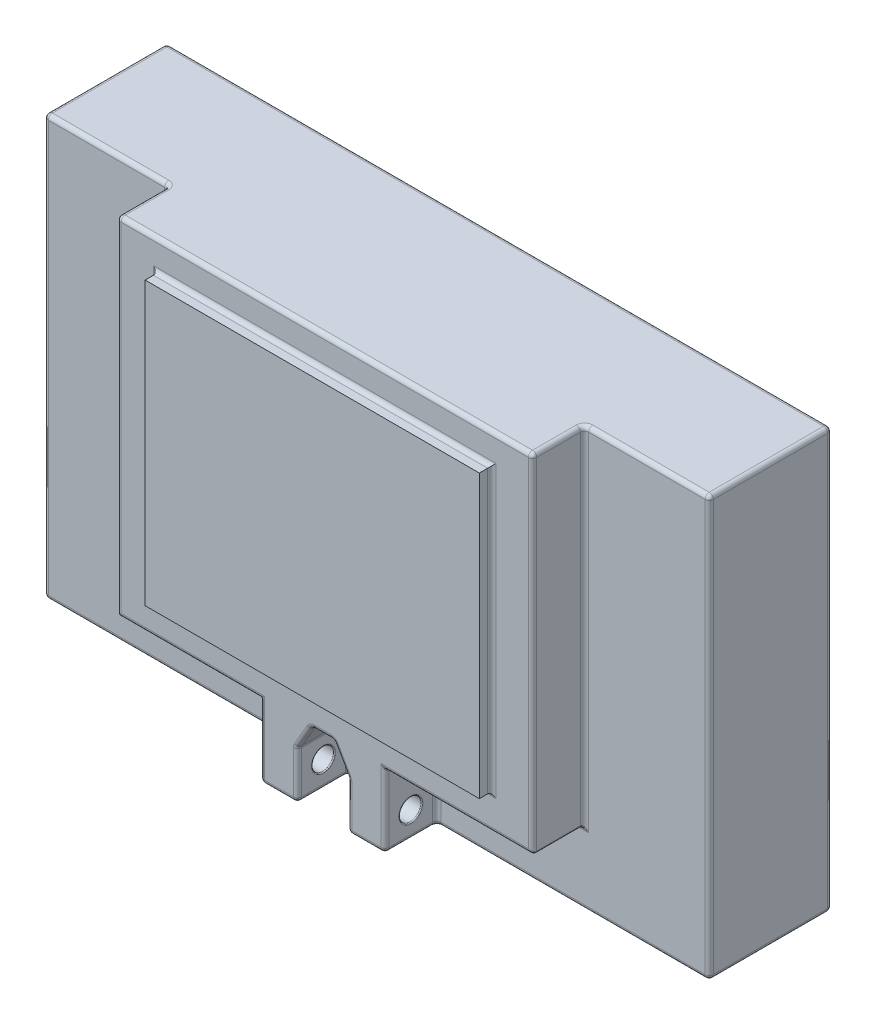
SolidWorks part; units mm, degrees
ref_plane "Front Plane" through (0, 0, 0) normal (0, 0, 1) x (1, 0, 0)
ref_plane "Top Plane" through (0, 0, 0) normal (0, 1, 0) x (1, 0, 0)
ref_plane "Right Plane" through (0, 0, 0) normal (1, 0, 0) x (0, 0, -1)
sketch "Sketch1" plane through (0, 0, 0) normal (0, 0, 1) x (1, 0, 0)
  line L1 (0, 0) -> (320, 0)
  line L2 (0, 0) -> (0, 202)
  line L3 (0, 202) -> (320, 202)
  line L4 (320, 0) -> (320, 202)
  dimension "D1" = 320
  dimension "D2" = 202
extrude "Boss-Extrude1" add sketch "Sketch1" along normal blind 84
sketch "Sketch2" plane through (0, 0, 84) normal (0, 0, 1) x (1, 0, 0)
  line L0 (320, 202) -> (0, 202) construction
  line L1 (240.4, 187.7) -> (79.6, 187.7)
  line L2 (240.4, 187.7) -> (240.4, 52)
  line L3 (240.4, 52) -> (79.6, 52)
  line L4 (79.6, 187.7) -> (79.6, 52)
  line L5 (160, 187.7) -> (160, 202) construction
  dimension "D1" = 14.3
  dimension "D2" = 160.8
  dimension "D3" = 135.7
sketch "Sketch3" plane through (0, 202, 0) normal (0, 1, 0) x (1, 0, 0)
  line L0 (320, -84) -> (0, -84) construction
  line L1 (260, -84) -> (320, -84)
  line L2 (260, -84) -> (260, -59)
  line L3 (260, -59) -> (320, -59)
  line L4 (320, -84) -> (320, -59)
  line L5 (320, -84) -> (320, 0) construction
  dimension "D1" = 25
  dimension "D2" = 60
extrude "Cut-Extrude2" cut sketch "Sketch3" against normal blind 280
sketch "Sketch4" plane through (0, 202, 0) normal (0, 1, 0) x (1, 0, 0)
  line L1 (0, -84) -> (60, -84)
  line L2 (0, -84) -> (0, -59)
  line L3 (0, -59) -> (60, -59)
  line L4 (60, -84) -> (60, -59)
  dimension "D1" = 25
  dimension "D2" = 60
extrude "Cut-Extrude3" cut sketch "Sketch4" against normal blind 280
sketch "Sketch5" plane through (60, 0, 0) normal (-1, 0, 0) x (0, 0, 1)
  line L0 (84, 202) -> (84, 0) construction
  line L1 (59, 0) -> (84, 0)
  line L2 (59, 0) -> (59, 35)
  line L3 (59, 35) -> (84, 35)
  line L4 (84, 0) -> (84, 35)
  dimension "D1" = 35
extrude "Cut-Extrude4" cut sketch "Sketch5" against normal blind 280
sketch "Sketch6" plane through (0, 0, 59) normal (0, 0, 1) x (1, 0, 0)
  line L1 (320, 0) -> (320, 202) construction
  line L2 (0, 0) -> (0, 202) construction
  line L3 (320, 0) -> (0, 0) construction
  line L4 (60, 202) -> (0, 202) construction
  point P0 (13, 187.9)
  point P1 (13, 14.1)
  point P2 (307, 14.1)
  point P3 (307, 187.9)
  dimension "D1" = 294
  dimension "D2" = 13
  dimension "D3" = 13
  dimension "D4" = 13
  dimension "D5" = 13
  dimension "D6" = 14.1
  dimension "D7" = 14.1
  dimension "D8" = 14.1
sketch "Sketch8" plane through (0, 0, 59) normal (0, 0, 1) x (1, 0, 0)
  line L0 (320, 0) -> (0, 0) construction
  line L1 (128.9599, 0) -> (188.9599, 0)
  line L2 (128.9599, 0) -> (128.9599, 35)
  line L3 (128.9599, 35) -> (188.9599, 35)
  line L4 (188.9599, 0) -> (188.9599, 35)
  line L5 (260, 35) -> (60, 35) construction
  dimension "D1" = 60
extrude "Boss-Extrude2" add sketch "Sketch8" along normal up to surface (25 mm away) up to face at (160, 118.5, 84)
sketch "Sketch9" plane through (0, 0, 84) normal (0, 0, 1) x (1, 0, 0)
  line L0 (146.9099, 0) -> (146.9099, 23)
  line L1 (188.9599, 0) -> (128.9599, 0) construction
  line L2 (146.9099, 23) -> (153.8381, 35)
  line L3 (153.8381, 35) -> (164.0817, 35)
  line L4 (164.0817, 35) -> (171.0099, 23)
  line L5 (171.0099, 23) -> (171.0099, 0)
  line L6 (128.9599, 35) -> (60, 35) construction
  line L7 (128.9599, 0) -> (128.9599, 35) construction
  line L9 (171.0099, 0) -> (146.9099, 0)
  dimension "D1" = 24.1
  dimension "D2" = 17.95
  dimension "D3" = 120
  dimension "D4" = 120
  dimension "D5" = 23
  dimension "D6" = 23
extrude "Cut-Extrude5" cut sketch "Sketch9" against normal up to surface (25 mm away) up to face at (256.32, 79, 59)
extrude "Boss-Extrude3" add sketch "Sketch2" along normal blind 6
fillet "Fillet1" radius 2 17 edges at (171.0099, 11.5, 84) (171.0099, 0, 71.5) (167.5458, 29, 84) (171.0099, 23, 71.5) (158.9599, 35, 84) (164.0817, 35, 71.5) (150.374, 29, 84) (153.8381, 35, 71.5) (146.9099, 0, 71.5) (146.9099, 11.5, 84) (146.9099, 23, 71.5) (146.9099, 11.5, 59) (150.374, 29, 59) (158.9599, 35, 59) (167.5458, 29, 59) (171.0099, 11.5, 59) (158.9599, 0, 59)
fillet "Fillet2" radius 2 16 edges at (254.48, 0, 59) (320, 101, 59) (260, 202, 71.5) (290, 202, 59) (0, 101, 59) (60, 202, 71.5) (30, 202, 59) (60, 118.5, 59) (260, 118.5, 59) (224.48, 35, 59) (94.48, 35, 59) (64.48, 0, 59) (188.9599, 0, 71.5) (188.9599, 17.5, 59) (128.9599, 0, 71.5) (128.9599, 17.5, 59)
fillet "Fillet3" radius 2 19 edges at (171.5957, 0.5858, 83.4142) (146.3241, 0.5858, 83.4142) (160, 187.7, 84) (79.6, 119.85, 84) (160, 52, 84) (240.4, 119.85, 84) (224.48, 35, 84) (188.9599, 18.5, 84) (188.3741, 0.5858, 84) (179.9849, 0, 84) (137.9349, 0, 84) (129.5457, 0.5858, 84) (128.9599, 18.5, 84) (94.48, 35, 84) (60, 117.5, 84) (60.5858, 201.4142, 84) (160, 202, 84) (259.4142, 201.4142, 84) (260, 117.5, 84)
fillet "Fillet4" radius 2 12 edges at (319.4142, 0.5858, 58.4142) (319.4142, 201.4142, 58.4142) (0.5858, 201.4142, 58.4142) (0.5858, 0.5858, 58.4142) (320, 0, 28.5) (320, 202, 28.5) (160, 0, 0) (320, 101, 0) (160, 202, 0) (0, 101, 0) (0, 202, 28.5) (0, 0, 28.5)
sketch "Sketch10" plane through (128.9599, 0, 0) normal (-1, 0, 0) x (0, 0, 1)
  line L0 (71.5, 12.3886) -> (71.5, 0) construction
  line L1 (82, 0) -> (61, 0) construction
  circle A0 centre (71.5, 12.3886) radius 5.25
  dimension "D1" = 10.5
extrude "Cut-Extrude6" cut sketch "Sketch10" against normal blind 68
fillet "Fillet5" radius 0.5 4 edges at (188.9599, 12.3886, 76.75) (171.0099, 12.3886, 66.25) (146.9099, 12.3886, 76.75) (128.9599, 12.3886, 76.75)
fillet "Fillet6" radius 1 12 edges at (60.5858, 35.5858, 83.4142) (59.4142, 34.4142, 59.5858) (129.5457, 35.5858, 83.4142) (128.3741, 34.4142, 59.5858) (188.3741, 35.5858, 83.4142) (189.5457, 34.4142, 59.5858) (259.4142, 35.5858, 83.4142) (260.5858, 34.4142, 59.5858) (60, 35, 71.5) (128.9599, 35, 71.5) (188.9599, 35, 71.5) (260, 35, 71.5)
sketch "Sketch11" plane through (0, 0, 0) normal (0, 0, -1) x (-1, 0, 0)
  text T0 "DRO" font "Century Gothic" height 100
extrude "Cut-Extrude7" cut sketch "Sketch11" against normal blind 10
